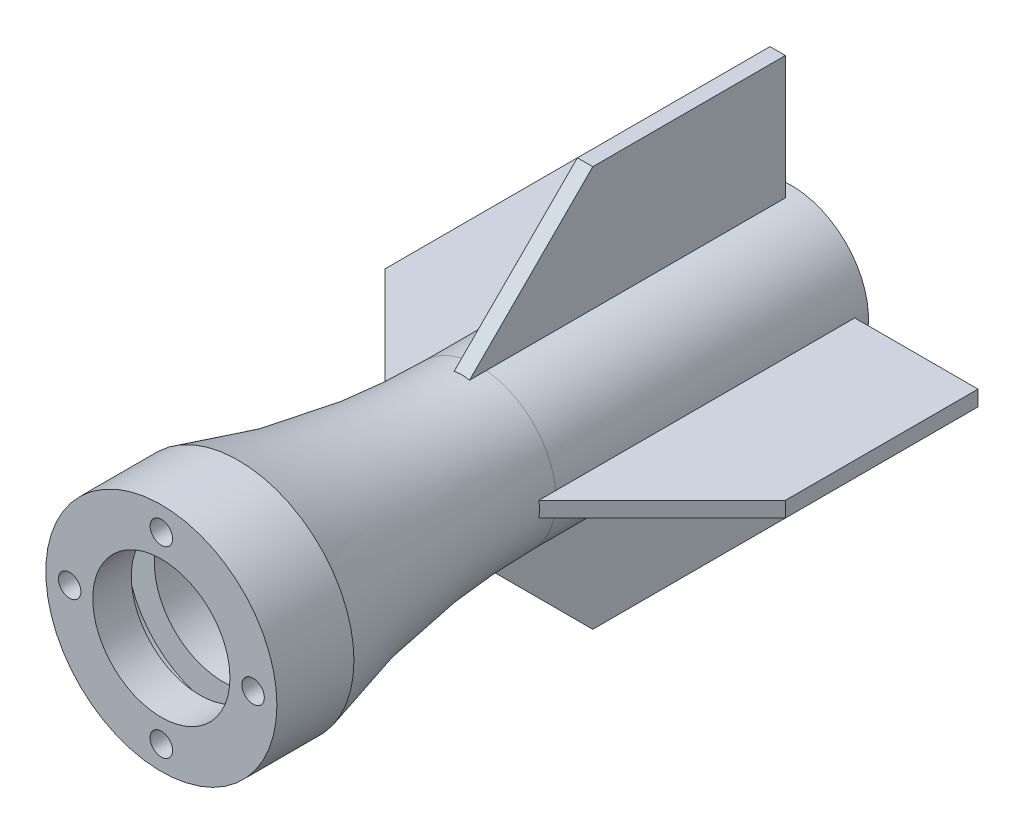
SolidWorks part; units mm, degrees
ref_plane "Front Plane" through (0, 0, 0) normal (0, 0, 1) x (1, 0, 0)
ref_plane "Top Plane" through (0, 0, 0) normal (0, 1, 0) x (1, 0, 0)
ref_plane "Right Plane" through (0, 0, 0) normal (1, 0, 0) x (0, 0, -1)
sketch "Sketch1" plane through (0, 0, 0) normal (0, 0, 1) x (1, 0, 0)
  circle A0 centre (0, 0) radius 12.7
  circle A1 centre (0, 0) radius 11.3081
  dimension "D1" = 25.4
  dimension "D2" = 22.6162
extrude "Boss-Extrude1" add sketch "Sketch1" along normal blind 101.6
sketch "Sketch2" plane through (0, 0, 0) normal (0, 1, 0) x (1, 0, 0)
  line L0 (-12.7, -52.07) -> (-33.02, -31.75)
  line L2 (-33.02, -31.75) -> (-33.02, 0)
  line L3 (-33.02, 0) -> (-12.7, 0)
  line L4 (-12.7, 0) -> (-12.7, -52.07)
  dimension "D1" = 20.32
  dimension "D2" = 12.7
  dimension "D3" = 31.75
  dimension "D4" = 52.07
  dimension "D5" = 45
extrude "Boss-Extrude4" add sketch "Sketch2" along normal mid plane 2.54 separate body
ref_axis "Axis1" through (0, 0, 101.6) along (0, 0, -1)
pattern_circular "CirPattern6" count 4 over 360 about axis through (0, 0, 101.6) along (0, 0, -1) of bodies 104
sketch "Sketch3" plane through (0, 0, 0) normal (0, 0, -1) x (-1, 0, 0)
  circle A0 centre (0, 0) radius 12.7
  circle A1 centre (0, 0) radius 1
  dimension "D1" = 2
  dimension "D2" = 25.4
extrude "Boss-Extrude5" add sketch "Sketch3" along normal blind 1
sketch "Sketch4" plane through (0, 0, -1) normal (0, 0, -1) x (-1, 0, 0)
  circle A0 centre (0, 0) radius 2
  circle A1 centre (0, 0) radius 12.7
  dimension "D1" = 4
  dimension "D2" = 25.4
extrude "O-Ring Body Hold" add sketch "Sketch4" along normal blind 1.27
ref_plane "Plane1" through (0, 0, 95.25) normal (0, 0, 1) x (1, 0, 0)
sketch "Sketch37" plane through (0, 0, 101.6) normal (0, 0, 1) x (1, 0, 0)
  circle A1 centre (0, 0) radius 19.05
  circle A2 centre (0, 0) radius 11.3081
  circle A3 centre (0, 0) radius 12.7 construction
  dimension "D1" = 38.1
  dimension "D2" = 22.6162
extrude "Boss-Extrude8" add sketch "Sketch37" against normal blind 12.7
sketch "Sketch38" plane through (0, 0, 101.6) normal (0, 0, 1) x (1, 0, 0)
  line L0 (0, 0) -> (-19.05, 0) construction
  line L1 (0, -19.05) -> (0, 19.05) construction
  line L2 (0, 0) -> (0, 19.05) construction
  line L3 (0, 0) -> (19.05, 0) construction
  line L4 (0, 0) -> (0, -19.05) construction
  circle A0 centre (0, 0) radius 19.05 construction
  circle A1 centre (-15.1181, 0) radius 1.8542
  circle A5 centre (0, 15.1181) radius 1.8542
  circle A6 centre (15.1181, 0) radius 1.8542
  circle A7 centre (0, -15.1181) radius 1.8542
  point P17 (-0.635, -0.635)
  point P24 (0, 0)
  dimension "D2" = 3.7084
  dimension "D1" = 15.1181
  dimension "D3" = 4
extrude "Cut-Extrude1" cut sketch "Sketch38" against normal blind 5.588
fillet "Fillet2" radius 127 1 edges at (12.7, 0, 88.9)
sketch "Sketch39" plane through (0, 0, 95.25) normal (0, 0, 1) x (1, 0, 0)
  circle A0 centre (0, 0) radius 19.05
  circle A1 centre (0, 0) radius 15.875
  circle A2 centre (0, 0) radius 19.05 construction
  circle A3 centre (0, 0) radius 10.16
  dimension "D1" = 3.175
  dimension "D2" = 20.32
extrude "Cut-Extrude2" cut sketch "Sketch39" against normal blind 3.81 contours A1 A3 region at (-15.426, 0, 95.25)
